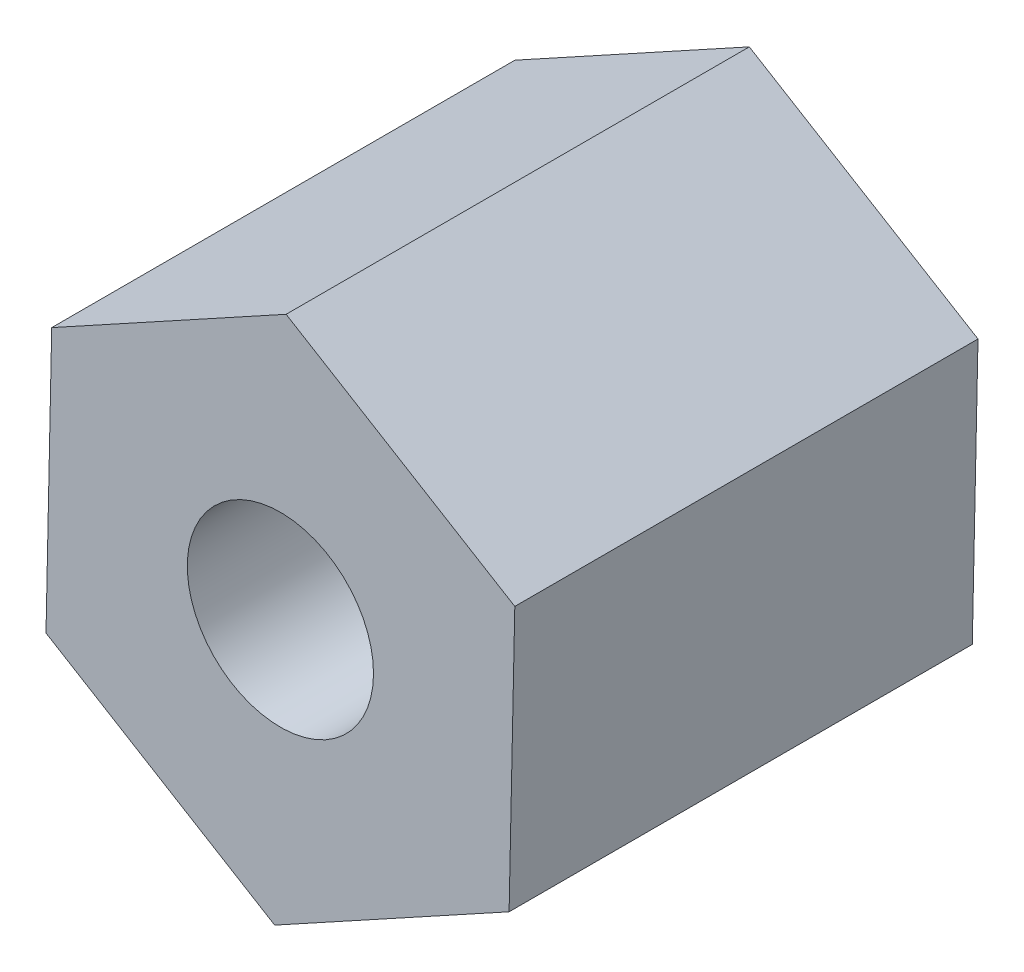
SolidWorks part; units mm, degrees
ref_plane "Front Plane" through (0, 0, 0) normal (0, 0, 1) x (1, 0, 0)
ref_plane "Top Plane" through (0, 0, 0) normal (0, 1, 0) x (1, 0, 0)
ref_plane "Right Plane" through (0, 0, 0) normal (1, 0, 0) x (0, 0, -1)
sketch "Thickness" plane through (0, 0, 0) normal (1, 0, 0) x (0, 0, -1)
  line L0 (0, 0) -> (-12.7, 0)
  dimension "D1" = 12.7
sketch "Sketch1" plane through (0, 0, 0) normal (0, 0, 1) x (1, 0, 0)
  line L1 (6.2702, -3.801) -> (6.4269, 3.5297)
  line L2 (6.4269, 3.5297) -> (0.1566, 7.3307)
  line L3 (0.1566, 7.3307) -> (-6.2702, 3.801)
  line L4 (-6.2702, 3.801) -> (-6.4269, -3.5297)
  line L5 (-6.4269, -3.5297) -> (-0.1566, -7.3307)
  line L6 (-0.1566, -7.3307) -> (6.2702, -3.801)
  circle A0 centre (0, 0) radius 6.35 construction
  dimension "D1" = 12.7
extrude "Boss-Extrude1" add sketch "Sketch1" along normal up to vertex (12.7 mm away) up to point (0, 0, 12.7)
hole_wizard "Tap Drill for 1/4-20 Tap1" positions "Sketch4" profile "Sketch3" hole size "1/4-20" standard "ANSI Inch" end condition through all
sketch "Sketch4" plane through (0, 0, 12.7) normal (0, 0, 1) x (1, 0, 0)
  point P0 (0, 0)
sketch "Sketch3" plane through (0, 0, 12.7) normal (1, 0, 0) x (0, -1, 0)
  line L0 (0, 0) -> (0, 12.7)
  line L1 (0, 12.7) -> (2.5527, 12.7)
  line L2 (2.5527, 12.7) -> (2.5527, 0)
  line L5 (2.5527, 0) -> (0, 0)
  line L11 (0, -6.35) -> (0, 107.95) construction
  dimension "Thru Hole Dia." = 5.1054
  dimension "Thru Hole Depth" = 12.7
